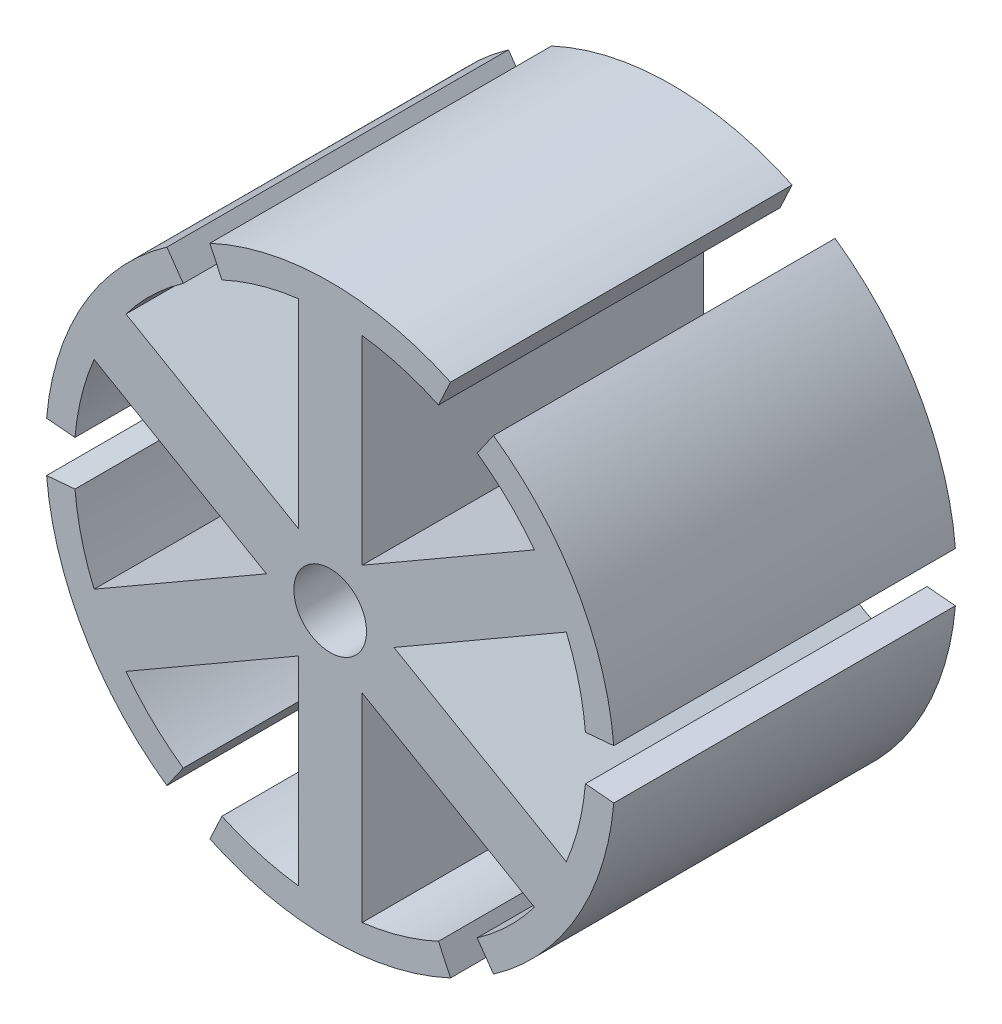
SolidWorks part; units mm, degrees
ref_plane "Front" through (0, 0, 0) normal (0, 0, 1) x (1, 0, 0)
ref_plane "Top" through (0, 0, 0) normal (0, 1, 0) x (1, 0, 0)
ref_plane "Right" through (0, 0, 0) normal (1, 0, 0) x (0, 0, -1)
sketch "Sketch1" plane through (0, 0, 0) normal (0, 0, 1) x (1, 0, 0)
  line L0 (0, 0) -> (25, 0) construction
  line L1 (0, 0) -> (12.5, 21.6506) construction
  line L2 (0, 0) -> (-12.5, 21.6506) construction
  line L3 (0, 0) -> (-25, 0) construction
  line L5 (0, 0) -> (-12.5, -21.6506) construction
  line L6 (0, 0) -> (12.5, -21.6506) construction
  line L7 (0, 0) -> (21.6506, 12.5) construction
  line L8 (5.6, 0) -> (20.7341, 8.7377) construction
  line L9 (2.8, 4.8497) -> (17.9341, 13.5874) construction
  line L10 (0, 0) -> (14.3394, 20.4788) construction
  line L14 (0, 0) -> (24.9049, 2.1789) construction
  line L16 (0, 0) -> (10.5655, 22.6577) construction
  line L17 (0, 0) -> (24.9049, -2.1789) construction
  circle A4 centre (0, 0) radius 25 construction
  circle A5 centre (0, 0) radius 22.5 construction
  circle A6 centre (0, 0) radius 5.6 construction
  dimension "D1" = 11.2
  dimension "D3" = 50
  dimension "D4" = 45
sketch "Sketch2" plane through (0, 0, 0) normal (0, 0, 1) x (1, 0, 0)
  line L0 (2.8, 4.8497) -> (17.9341, 13.5874)
  line L1 (5.6, 0) -> (20.7341, 8.7377)
  line L2 (0, 0) -> (14.3394, 20.4788) construction
  line L3 (0, 0) -> (24.9049, 2.1789) construction
  line L4 (22.4144, 1.961) -> (24.9049, 2.1789)
  line L5 (12.9055, 18.4309) -> (14.3394, 20.4788)
  line L6 (5.6, 0) -> (20.7341, -8.7377)
  line L7 (22.4144, -1.961) -> (24.9049, -2.1789)
  line L8 (12.9055, -18.4309) -> (14.3394, -20.4788)
  line L9 (2.8, -4.8497) -> (17.9341, -13.5874)
  line L10 (2.8, -4.8497) -> (2.8, -22.3251)
  line L11 (9.5089, -20.3919) -> (10.5655, -22.6577)
  line L12 (-9.5089, -20.3919) -> (-10.5655, -22.6577)
  line L13 (-2.8, -4.8497) -> (-2.8, -22.3251)
  line L14 (-2.8, -4.8497) -> (-17.9341, -13.5874)
  line L15 (-12.9055, -18.4309) -> (-14.3394, -20.4788)
  line L16 (-22.4144, -1.961) -> (-24.9049, -2.1789)
  line L17 (-5.6, 0) -> (-20.7341, -8.7377)
  line L18 (-5.6, 0) -> (-20.7341, 8.7377)
  line L19 (-22.4144, 1.961) -> (-24.9049, 2.1789)
  line L20 (-12.9055, 18.4309) -> (-14.3394, 20.4788)
  line L21 (-2.8, 4.8497) -> (-17.9341, 13.5874)
  line L22 (-2.8, 4.8497) -> (-2.8, 22.3251)
  line L23 (-9.5089, 20.3919) -> (-10.5655, 22.6577)
  line L24 (9.5089, 20.3919) -> (10.5655, 22.6577)
  line L25 (2.8, 4.8497) -> (2.8, 22.3251)
  arc A0 (22.4144, -1.961) -> (20.7341, -8.7377) centre (0, 0) cw
  arc A1 (12.9055, 18.4309) -> (17.9341, 13.5874) centre (0, 0) cw
  circle A2 centre (0, 0) radius 22.5 construction
  arc A3 (20.7341, 8.7377) -> (22.4144, 1.961) centre (0, 0) cw
  arc A4 (14.3394, 20.4788) -> (24.9049, 2.1789) centre (0, 0) cw
  arc A5 (24.9049, -2.1789) -> (14.3394, -20.4788) centre (0, 0) cw
  arc A6 (17.9341, -13.5874) -> (12.9055, -18.4309) centre (0, 0) cw
  arc A7 (9.5089, -20.3919) -> (2.8, -22.3251) centre (0, 0) cw
  arc A8 (10.5655, -22.6577) -> (-10.5655, -22.6577) centre (0, 0) cw
  arc A9 (-2.8, -22.3251) -> (-9.5089, -20.3919) centre (0, 0) cw
  arc A10 (-12.9055, -18.4309) -> (-17.9341, -13.5874) centre (0, 0) cw
  arc A11 (-14.3394, -20.4788) -> (-24.9049, -2.1789) centre (0, 0) cw
  arc A12 (-20.7341, -8.7377) -> (-22.4144, -1.961) centre (0, 0) cw
  arc A13 (-22.4144, 1.961) -> (-20.7341, 8.7377) centre (0, 0) cw
  arc A14 (-24.9049, 2.1789) -> (-14.3394, 20.4788) centre (0, 0) cw
  arc A15 (-17.9341, 13.5874) -> (-12.9055, 18.4309) centre (0, 0) cw
  arc A16 (-9.5089, 20.3919) -> (-2.8, 22.3251) centre (0, 0) cw
  arc A17 (-10.5655, 22.6577) -> (10.5655, 22.6577) centre (0, 0) cw
  arc A18 (2.8, 22.3251) -> (9.5089, 20.3919) centre (0, 0) cw
  point P64 (0, 0)
  dimension "D2" = 25
  dimension "D3" = 22.4144
  dimension "D4" = 21.1309
  dimension "D1" = 6
extrude "Boss-Extrude1" add sketch "Sketch2" along normal blind 30
sketch "Sketch4" plane through (0, 0, 0) normal (0, 0, -1) x (-1, 0, 0)
  circle A0 centre (0, 0) radius 3.19 construction
  circle A1 centre (0, 0) radius 3.19
extrude "Cut-Extrude1" cut sketch "Sketch4" against normal blind 30 contours A1
